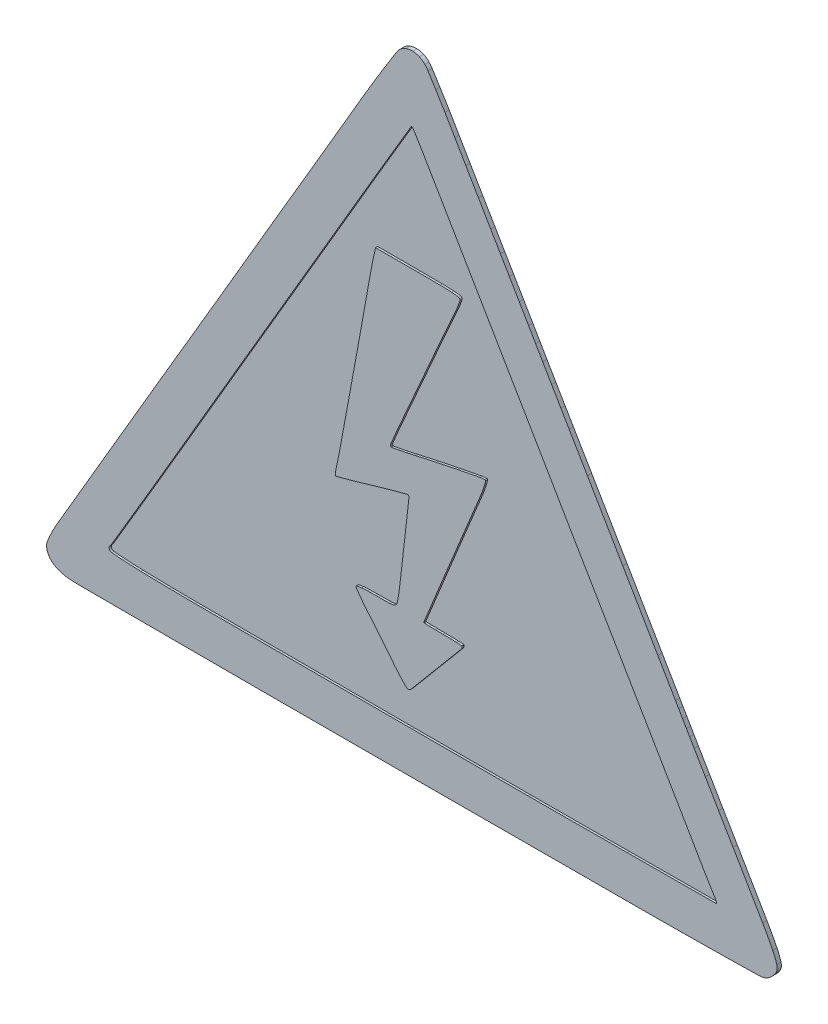
SolidWorks part; units mm, degrees
ref_plane "Front Plane" through (0, 0, 0) normal (0, 0, 1) x (1, 0, 0)
ref_plane "Top Plane" through (0, 0, 0) normal (0, 1, 0) x (1, 0, 0)
ref_plane "Right Plane" through (0, 0, 0) normal (1, 0, 0) x (0, 0, -1)
sketch "Model" plane through (0, 0, 0) normal (0, 0, 1) x (1, 0, 0)
  line L0 (254.5174, 562.263) -> (254.2527, 530.6011)
  line L1 (254.0503, 485.6583) -> (254, 402.9167)
  line L2 (254, 402.9167) -> (254, 243)
  line L3 (254, 243) -> (435, 243)
  line L4 (435, 243) -> (616, 243)
  line L5 (616, 243) -> (616, 402.8834)
  line L6 (616, 402.8834) -> (616, 562.7667)
  line L7 (616, 562.7667) -> (613.75, 563.3641)
  line L8 (609.6508, 563.899) -> (434.1478, 563.8938)
  line L9 (434.1478, 563.8938) -> (258.0026, 563.8779)
  line L10 (614.7531, 403.25) -> (614.5, 244.5)
  line L11 (614.5, 244.5) -> (434.75, 244.2473)
  line L12 (434.75, 244.2473) -> (255, 243.9946)
  line L13 (255, 243.9946) -> (255, 402.9973)
  line L14 (255, 402.9973) -> (255, 562)
  line L15 (255, 562) -> (435.0031, 562)
  line L16 (435.0031, 562) -> (615.0062, 562)
  line L17 (615.0062, 562) -> (614.7531, 403.25)
  line L18 (409.4482, 516) -> (401.9391, 503.113)
  line L19 (401.9391, 503.113) -> (394.0604, 489.6125)
  line L20 (394.0604, 489.6125) -> (386.9212, 477.3967)
  line L21 (386.9212, 477.3967) -> (382, 469)
  line L22 (382, 469) -> (377.0758, 460.6035)
  line L23 (377.0758, 460.6035) -> (369.926, 448.3875)
  line L24 (369.926, 448.3875) -> (362.0323, 434.887)
  line L25 (362.0323, 434.887) -> (354.5055, 422)
  line L26 (354.5055, 422) -> (347.0845, 409.2961)
  line L27 (347.0845, 409.2961) -> (339.5095, 396.3469)
  line L28 (339.5095, 396.3469) -> (332.7922, 384.8794)
  line L29 (332.7922, 384.8794) -> (328.4562, 377.5)
  line L30 (328.4562, 377.5) -> (323.8759, 369.703)
  line L31 (323.8759, 369.703) -> (315.943, 356.1562)
  line L32 (315.943, 356.1562) -> (306.7606, 340.4578)
  line L33 (306.7606, 340.4578) -> (297.437, 324.5)
  line L34 (297.437, 324.5) -> (288.2901, 308.8389)
  line L35 (288.2901, 308.8389) -> (279.64, 294.0345)
  line L36 (279.64, 294.0345) -> (272.3357, 281.5384)
  line L37 (272.3357, 281.5384) -> (268.8317, 275.5535)
  line L38 (277.3622, 254.2835) -> (324.2251, 254.1769)
  line L39 (377.4221, 254.1321) -> (439.5442, 254.2008)
  line L40 (439.5442, 254.2008) -> (540.6639, 254.4275)
  line L41 (586.7985, 301.366) -> (580.0001, 312.9433)
  line L42 (580.0001, 312.9433) -> (573.7295, 323.631)
  line L43 (573.7295, 323.631) -> (568.474, 332.5964)
  line L44 (568.474, 332.5964) -> (566.3419, 336.25)
  line L45 (566.3419, 336.25) -> (564.8206, 338.8676)
  line L46 (564.8206, 338.8676) -> (563.0002, 342)
  line L47 (563.0002, 342) -> (561.1798, 345.1324)
  line L48 (561.1798, 345.1324) -> (559.6587, 347.75)
  line L49 (559.6587, 347.75) -> (551.3542, 361.9993)
  line L50 (551.3542, 361.9993) -> (534.7422, 390.406)
  line L51 (534.7422, 390.406) -> (518.1219, 418.8013)
  line L52 (518.1219, 418.8013) -> (509.4906, 433.5)
  line L53 (509.4906, 433.5) -> (505.602, 440.1185)
  line L54 (505.602, 440.1185) -> (501.2118, 447.6188)
  line L55 (501.2118, 447.6188) -> (497.0005, 454.8357)
  line L56 (497.0005, 454.8357) -> (493.7108, 460.5)
  line L57 (493.7108, 460.5) -> (490.3642, 466.2613)
  line L58 (490.3642, 466.2613) -> (485.9508, 473.8219)
  line L59 (485.9508, 473.8219) -> (481.2765, 481.8054)
  line L60 (481.2765, 481.8054) -> (477.0492, 489)
  line L61 (477.0492, 489) -> (472.4883, 496.7622)
  line L62 (472.4883, 496.7622) -> (466.73, 506.5921)
  line L63 (466.73, 506.5921) -> (460.7774, 516.7741)
  line L64 (460.7774, 516.7741) -> (455.5617, 525.7179)
  line L65 (439.7439, 513.25) -> (448.2116, 498.8127)
  line L66 (448.2116, 498.8127) -> (474.0617, 454.5883)
  line L67 (474.0617, 454.5883) -> (501.7789, 407.1576)
  line L68 (506.2536, 399.4159) -> (514.1781, 385.8687)
  line L69 (514.1781, 385.8687) -> (523.4248, 370.0728)
  line L70 (523.4248, 370.0728) -> (534.0136, 352)
  line L71 (534.0136, 352) -> (544.9984, 333.2438)
  line L72 (544.9984, 333.2438) -> (555.4669, 315.3406)
  line L73 (555.4669, 315.3406) -> (564.3298, 300.1587)
  line L74 (564.3298, 300.1587) -> (568.7752, 292.5)
  line L75 (568.7752, 292.5) -> (571.75, 287.3769)
  line L76 (571.75, 287.3769) -> (574.4768, 282.7393)
  line L77 (574.4768, 282.7393) -> (576.784, 278.8624)
  line L78 (578.6817, 274.4575) -> (536.8469, 274.2284)
  line L79 (490.5252, 274.0559) -> (435.5, 274)
  line L80 (435.5, 274) -> (336.3638, 274.0533)
  line L81 (293.538, 278.3853) -> (303.7518, 295.6991)
  line L82 (303.7518, 295.6991) -> (315.1697, 315.1202)
  line L83 (315.1697, 315.1202) -> (328.5545, 338)
  line L84 (328.5545, 338) -> (342.2047, 361.3749)
  line L85 (342.2047, 361.3749) -> (354.4703, 382.3719)
  line L86 (354.4703, 382.3719) -> (364.7892, 400.0313)
  line L87 (364.7892, 400.0313) -> (367.9921, 405.5)
  line L88 (367.9921, 405.5) -> (370.7197, 410.1541)
  line L89 (370.7197, 410.1541) -> (375.9419, 419.0813)
  line L90 (375.9419, 419.0813) -> (382.0778, 429.5763)
  line L91 (382.0778, 429.5763) -> (388.4609, 440.5)
  line L92 (388.4609, 440.5) -> (415.4147, 486.6123)
  line L93 (427.2245, 506.6978) -> (434.9144, 519.693)
  line L94 (435.644, 519.8958) -> (436.8451, 518.0172)
  line L95 (416.5729, 454.4409) -> (415.7612, 450.1768)
  line L96 (415.7612, 450.1768) -> (414.8621, 445.3116)
  line L97 (414.8621, 445.3116) -> (413.9955, 440.4742)
  line L98 (410.5497, 421.2358) -> (405.8867, 395.7753)
  line L99 (405.8867, 395.7753) -> (401.131, 370.0554)
  line L100 (399.5886, 359.3109) -> (404.4517, 360.6285)
  line L101 (428.4417, 367.4781) -> (433.2859, 368.7501)
  line L102 (433.954, 367.8965) -> (431.5999, 347.0412)
  line L103 (417.384, 307.9395) -> (420.5734, 304.0364)
  line L104 (420.5734, 304.0364) -> (423.7854, 300.0641)
  line L105 (434.9417, 290.0359) -> (446.734, 304.0528)
  line L106 (446.734, 304.0528) -> (458.4976, 318.1032)
  line L107 (443.6438, 320.0814) -> (441.1091, 320.1642)
  line L108 (441.105, 320.8098) -> (450.391, 343.4461)
  line L109 (450.391, 343.4461) -> (459.2078, 364.8667)
  line L110 (428.9777, 384.7949) -> (425.7191, 384.1924)
  line L111 (429.2627, 394.5496) -> (436.7188, 411.5)
  line L112 (436.7188, 411.5) -> (439.8423, 418.5953)
  line L113 (439.8423, 418.5953) -> (443.0328, 425.8562)
  line L114 (443.0328, 425.8562) -> (445.8621, 432.3068)
  line L115 (445.8621, 432.3068) -> (447.6939, 436.5)
  line L116 (447.6939, 436.5) -> (449.2754, 440.0969)
  line L117 (449.2754, 440.0969) -> (451.1566, 444.3102)
  line L118 (451.1566, 444.3102) -> (453.0318, 448.4617)
  line L119 (453.0318, 448.4617) -> (454.589, 451.8538)
  line L120 (438.0829, 462) -> (418.1657, 462)
  line L121 (418.1657, 462) -> (417.1114, 457.0838)
  arc A0 (255.25, 563.3406) -> (254.5174, 562.263) centre (255.6915, 562.2525) ccw
  arc A1 (254.2527, 530.6011) -> (254.0503, 485.6583) centre (7088.4974, 477.3474) ccw
  arc A2 (613.75, 563.3641) -> (609.6508, 563.899) centre (609.6506, 547.9236) ccw
  arc A3 (258.0026, 563.8779) -> (255.25, 563.3406) centre (258.0034, 556.5551) ccw
  arc A4 (429.6585, 548.75) -> (428.1385, 546.925) centre (435.6643, 542.2023) ccw
  arc A5 (428.1385, 546.925) -> (422.7099, 538.2016) centre (1587.9194, -180.862) ccw
  arc A6 (422.7099, 538.2016) -> (416.4302, 527.8498) centre (1098.4506, 121.1954) ccw
  arc A7 (416.4302, 527.8498) -> (409.4482, 516) centre (1549.716, -147.8722) ccw
  arc A8 (268.8317, 275.5535) -> (266.4985, 271.3767) centre (367.7126, 217.5792) ccw
  arc A9 (266.4985, 271.3767) -> (264.6345, 267.5964) centre (327.6097, 238.8948) ccw
  arc A10 (264.6345, 267.5964) -> (263.3176, 264.4636) centre (316.7115, 243.8618) ccw
  arc A11 (263.3176, 264.4636) -> (263, 262.7581) centre (267.7379, 262.7581) ccw
  arc A12 (263, 262.7581) -> (263.7034, 259.7511) centre (269.779, 262.7581) ccw
  arc A13 (263.7034, 259.7511) -> (265.6781, 257.2792) centre (270.3649, 263.048) ccw
  arc A14 (265.6781, 257.2792) -> (268.876, 255.506) centre (272.2628, 265.3841) ccw
  arc A15 (268.876, 255.506) -> (273.1158, 254.5395) centre (275.5296, 274.9119) ccw
  arc A16 (273.1158, 254.5395) -> (277.3622, 254.2835) centre (277.455, 291.1629) ccw
  arc A17 (324.2251, 254.1769) -> (377.4221, 254.1321) centre (369.5619, 22530.9204) ccw
  arc A18 (540.6639, 254.4275) -> (577.9127, 254.7154) centre (531.0837, 3903.5293) ccw
  arc A19 (577.9127, 254.7154) -> (599.4836, 255.1033) centre (551.0115, 2350.783) ccw
  arc A20 (599.4836, 255.1033) -> (603.3397, 256.3029) centre (599.3137, 262.4469) ccw
  arc A21 (603.3397, 256.3029) -> (604.4762, 257.1751) centre (598.0642, 264.3537) ccw
  arc A22 (604.4762, 257.1751) -> (605.6159, 258.3071) centre (594.3736, 268.4856) ccw
  arc A23 (605.6159, 258.3071) -> (606.5931, 259.5106) centre (594.9263, 267.9852) ccw
  arc A24 (606.5931, 259.5106) -> (607.2248, 260.594) centre (601.5284, 263.1895) ccw
  arc A25 (607.2248, 260.594) -> (607.4539, 263.7582) centre (603.0748, 262.4849) ccw
  arc A26 (607.4539, 263.7582) -> (605.5395, 268.6405) centre (579.6678, 255.6791) ccw
  arc A27 (605.5395, 268.6405) -> (600.7905, 277.4259) centre (462.0726, 196.7652) ccw
  arc A28 (600.7905, 277.4259) -> (586.7985, 301.366) centre (-4778.7635, -2850.6336) ccw
  arc A29 (455.5617, 525.7179) -> (450.8812, 533.6467) centre (-211.2737, 137.4217) ccw
  arc A30 (450.8812, 533.6467) -> (446.5578, 540.7405) centre (11.4825, 270.7163) ccw
  arc A31 (446.5578, 540.7405) -> (442.8529, 546.6384) centre (-98.3746, 202.5343) ccw
  arc A32 (442.8529, 546.6384) -> (441.4422, 548.4679) centre (432.073, 539.7847) ccw
  arc A33 (441.4422, 548.4679) -> (438.8438, 550.3226) centre (435.6481, 543.0981) ccw
  arc A34 (438.8438, 550.3226) -> (435.6893, 551.0287) centre (435.4909, 542.7426) ccw
  arc A35 (435.6893, 551.0287) -> (432.4617, 550.4774) centre (435.4851, 542.5) ccw
  arc A36 (432.4617, 550.4774) -> (429.6585, 548.75) centre (435.5512, 542.3257) ccw
  arc A37 (504.7595, 402) -> (501.7789, 407.1576) centre (-34.2028, 93.9646) ccw
  arc A38 (504.7595, 402) -> (506.2536, 399.4159) centre (764.8519, 550.6522) ccw
  arc A39 (576.784, 278.8624) -> (577.6416, 277.5275) centre (598.0405, 291.5754) ccw
  arc A40 (578.1616, 276.7153) -> (577.6416, 277.5275) centre (565.8108, 269.3801) ccw
  arc A41 (578.601, 275.906) -> (578.1616, 276.7153) centre (567.8926, 270.6165) ccw
  arc A42 (578.9183, 275.1979) -> (578.601, 275.906) centre (569.3193, 271.3213) ccw
  arc A43 (579, 274.7775) -> (578.9183, 275.1979) centre (577.8772, 274.7775) ccw
  arc A44 (578.6817, 274.4575) -> (579, 274.7775) centre (578.68, 274.7775) ccw
  arc A45 (490.5252, 274.0559) -> (536.8469, 274.2284) centre (462.7655, 13946.4121) ccw
  arc A46 (307.5192, 274.4278) -> (336.3638, 274.0533) centre (337.666, 1485.3395) ccw
  arc A47 (293.7652, 275.2491) -> (307.5192, 274.4278) centre (312.4538, 472.6438) ccw
  arc A48 (292.9063, 277.55) -> (293.7652, 275.2491) centre (293.8939, 276.6079) ccw
  arc A49 (292.9063, 277.55) -> (293.538, 278.3853) centre (289.5865, 280.7171) ccw
  arc A50 (427.2245, 506.6978) -> (415.4147, 486.6123) centre (4761.3047, -2055.1596) ccw
  arc A51 (435.4532, 520) -> (434.9144, 519.693) centre (435.4532, 519.3738) ccw
  arc A52 (435.644, 519.8958) -> (435.4532, 520) centre (435.4532, 519.7731) ccw
  arc A53 (438.1982, 515.8378) -> (436.8451, 518.0172) centre (334.8766, 453.1996) ccw
  arc A54 (439.7439, 513.25) -> (438.1982, 515.8378) centre (242.0352, 396.9152) ccw
  arc A55 (417.1114, 457.0838) -> (416.5729, 454.4409) centre (545.7867, 429.4879) ccw
  arc A56 (410.5497, 421.2358) -> (413.9955, 440.4742) centre (-3126.8024, 1064.7317) ccw
  arc A57 (399.9285, 364.1812) -> (401.131, 370.0554) centre (242.2768, 399.5117) ccw
  arc A58 (399.9285, 364.1812) -> (399.5712, 362.4526) centre (451.8194, 352.5521) ccw
  arc A59 (399.5712, 362.4526) -> (399.3243, 360.9413) centre (429.2539, 356.828) ccw
  arc A60 (399.3243, 360.9413) -> (399.1698, 359.6826) centre (442.8629, 354.9577) ccw
  arc A61 (399.1698, 359.6826) -> (399.2709, 359.3958) centre (399.5199, 359.6448) ccw
  arc A62 (399.2709, 359.3958) -> (399.5886, 359.3109) centre (399.5031, 359.628) ccw
  arc A63 (404.4517, 360.6285) -> (409.9578, 362.1713) centre (302.2874, 735.8597) ccw
  arc A64 (409.9578, 362.1713) -> (416.4318, 364.0682) centre (202.2388, 1083.0903) ccw
  arc A65 (422.9129, 365.9577) -> (416.4318, 364.0682) centre (581.3911, -189.6782) ccw
  arc A66 (428.4417, 367.4781) -> (422.9129, 365.9577) centre (505.7608, 75.4872) ccw
  arc A67 (433.6941, 368.6392) -> (433.2859, 368.7501) centre (433.3932, 368.3383) ccw
  arc A68 (433.954, 367.8965) -> (433.6941, 368.6392) centre (433.0528, 367.9979) ccw
  arc A69 (429.4091, 328.0999) -> (431.5999, 347.0412) centre (-3499.2151, 792.0971) ccw
  arc A70 (428.4419, 322.25) -> (429.4091, 328.0999) centre (365.7964, 335.6131) ccw
  arc A71 (427.8062, 320.9914) -> (428.4419, 322.25) centre (425.7345, 322.8275) ccw
  arc A72 (426.6738, 320.322) -> (427.8062, 320.9914) centre (426.2013, 322.4138) ccw
  arc A73 (424.4129, 320.0504) -> (426.6738, 320.322) centre (424.2241, 331.167) ccw
  arc A74 (418.4809, 320) -> (424.4129, 320.0504) centre (418.4812, 669.3673) ccw
  arc A75 (418.4809, 320) -> (414.6029, 319.9339) centre (418.4809, 206.1838) ccw
  arc A76 (414.6029, 319.9339) -> (411.601, 319.7234) centre (416.03, 278.0724) ccw
  arc A77 (411.601, 319.7234) -> (409.3653, 319.4218) centre (415.836, 279.8974) ccw
  arc A78 (409.3653, 319.4218) -> (409, 318.9918) centre (409.4357, 318.9918) ccw
  arc A79 (409, 318.9918) -> (409.2014, 318.3497) centre (410.1244, 318.9918) ccw
  arc A80 (409.2014, 318.3497) -> (410.6891, 316.2623) centre (501.4444, 382.5187) ccw
  arc A81 (410.6891, 316.2623) -> (412.5468, 313.8204) centre (473.4453, 362.0778) ccw
  arc A82 (412.5468, 313.8204) -> (414.75, 311.1157) centre (514.0862, 394.2823) ccw
  arc A83 (417.384, 307.9395) -> (414.75, 311.1157) centre (76.0052, 27.5113) ccw
  arc A84 (426.5, 296.6603) -> (423.7854, 300.0641) centre (14.2632, -29.328) ccw
  arc A85 (426.5, 296.6603) -> (428.8828, 293.7681) centre (499.8678, 354.6781) ccw
  arc A86 (428.8828, 293.7681) -> (431.0761, 291.3644) centre (469.3589, 328.4995) ccw
  arc A87 (431.0761, 291.3644) -> (432.9665, 289.4906) centre (479.7851, 338.6131) ccw
  arc A88 (432.9665, 289.4906) -> (433.6528, 289.2864) centre (433.5095, 290.0602) ccw
  arc A89 (433.6528, 289.2864) -> (434.9417, 290.0359) centre (433.2496, 291.4628) ccw
  arc A90 (458.4976, 318.1032) -> (459, 319.4885) centre (456.839, 319.4885) ccw
  arc A91 (459, 319.4885) -> (458.8073, 319.6951) centre (458.7929, 319.4885) ccw
  arc A92 (458.8073, 319.6951) -> (456.3563, 319.8497) centre (445.2152, 123.8181) ccw
  arc A93 (456.3563, 319.8497) -> (453.451, 319.9632) centre (451.7039, 237.9905) ccw
  arc A94 (453.451, 319.9632) -> (450, 320) centre (449.9999, 158.0305) ccw
  arc A95 (446.549, 320.0199) -> (450, 320) centre (449.9999, 618.953) ccw
  arc A96 (443.6438, 320.0814) -> (446.549, 320.0199) centre (448.2924, 471.0463) ccw
  arc A97 (441, 320.2771) -> (441.1091, 320.1642) centre (441.113, 320.2771) ccw
  arc A98 (441.105, 320.8098) -> (441, 320.2771) centre (442.4036, 320.2771) ccw
  arc A99 (466.8368, 383.25) -> (459.2078, 364.8667) centre (5650.1709, -1778.5824) ccw
  arc A100 (466.8368, 383.25) -> (468.4571, 387.3169) centre (340.4994, 435.942) ccw
  arc A101 (468.4571, 387.3169) -> (469.4871, 390.3802) centre (429.4944, 402.1232) ccw
  arc A102 (469.4871, 390.3802) -> (470.0423, 392.5769) centre (440.9404, 398.7623) ccw
  arc A103 (470.0423, 392.5769) -> (469.6996, 393) centre (469.6996, 392.6497) ccw
  arc A104 (469.6996, 393) -> (467.2758, 392.7684) centre (469.6996, 380.2008) ccw
  arc A105 (467.2758, 392.7684) -> (457.4121, 390.836) centre (791.877, -1290.2576) ccw
  arc A106 (457.4121, 390.836) -> (446.9007, 388.6748) centre (621.2657, -432.7298) ccw
  arc A107 (446.9007, 388.6748) -> (437.125, 386.5191) centre (578.9666, -233.4657) ccw
  arc A108 (432.7364, 385.5493) -> (437.125, 386.5191) centre (369.7434, 681.0418) ccw
  arc A109 (428.9777, 384.7949) -> (432.7364, 385.5493) centre (399.2579, 542.5933) ccw
  arc A110 (425.3629, 384.3038) -> (425.7191, 384.1924) centre (425.6473, 384.5882) ccw
  arc A111 (425.2291, 384.9468) -> (425.3629, 384.3038) centre (425.7864, 384.7273) ccw
  arc A112 (426.6493, 388.4477) -> (425.2291, 384.9468) centre (598.1218, 316.8487) ccw
  arc A113 (429.2627, 394.5496) -> (426.6493, 388.4477) centre (762.9976, 248.004) ccw
  arc A114 (454.589, 451.8538) -> (455.8955, 454.7722) centre (346.383, 502.044) ccw
  arc A115 (455.8955, 454.7722) -> (456.998, 457.4575) centre (381.4271, 486.917) ccw
  arc A116 (456.998, 457.4575) -> (457.8463, 459.7219) centre (372.1344, 490.5395) ccw
  arc A117 (457.8463, 459.7219) -> (458, 460.6038) centre (455.3934, 460.6038) ccw
  arc A118 (458, 460.6038) -> (457.3532, 461.3643) centre (457.2295, 460.6038) ccw
  arc A119 (457.3532, 461.3643) -> (454.1837, 461.7325) centre (451.7387, 426.8545) ccw
  arc A120 (454.1837, 461.7325) -> (448.7484, 461.9489) centre (447.8845, 371.8726) ccw
  arc A121 (448.7484, 461.9489) -> (438.0829, 462) centre (438.0834, -649.9393) ccw
extrude "Saliente-Extruir1" add sketch "Model" along normal blind 2 contours A35 A36 A4 A5 A6 A7 L18 L19 L20 L21 L22 L23 L24 L25 L26 L27 L28 L29 L30 L31 L32 L33 L34 L35 L36 L37 A8 A9 A10 A11 A12 A13 A14 A15 A16 L38 A17 L39 L40 A18 A19 A20 A21 A22 A23 A24 A25 A26 A27 A28 L41 | A120 A121 L120 L121 A55 L95 L96 L97 A56 L98 L99 A57 A58 A59 A60 A61 A62 L100 A63 A64 A65 A66 L101 A67 A68 L102 A69 A70 A71 A72 A73 A74 A75 A76 A77 A78 A79 A80 A81 A82 A83 L103 L104 A84 A85 A86 A87 A88 A89 L105 L106 region at (416.8429, 519.6248, 0) region at (432.4463, 383.6135, 0)
extrude "Saliente-Extruir2" add sketch "Model<3>" along normal blind 1 contours L65 A54 A53 L94 A52 A51 L93 A50 L92 L91 L90 L89 L88 L87 L86 L85 L84 L83 L82 L81 A49 A48 A47 A46 L80 L79 A45 L78 A44 A43 A42 A41 A40 A39 L77 L76 L75 L74 L73 L72 L71 L70 L69 L68 A38 A37 L67 L66 A121 A120 region at (440.7207, 504.121, 0)
sketch "Model<3>" plane through (0, 0, 0) normal (0, 0, 1) x (1, 0, 0) same geometry as "Model"
